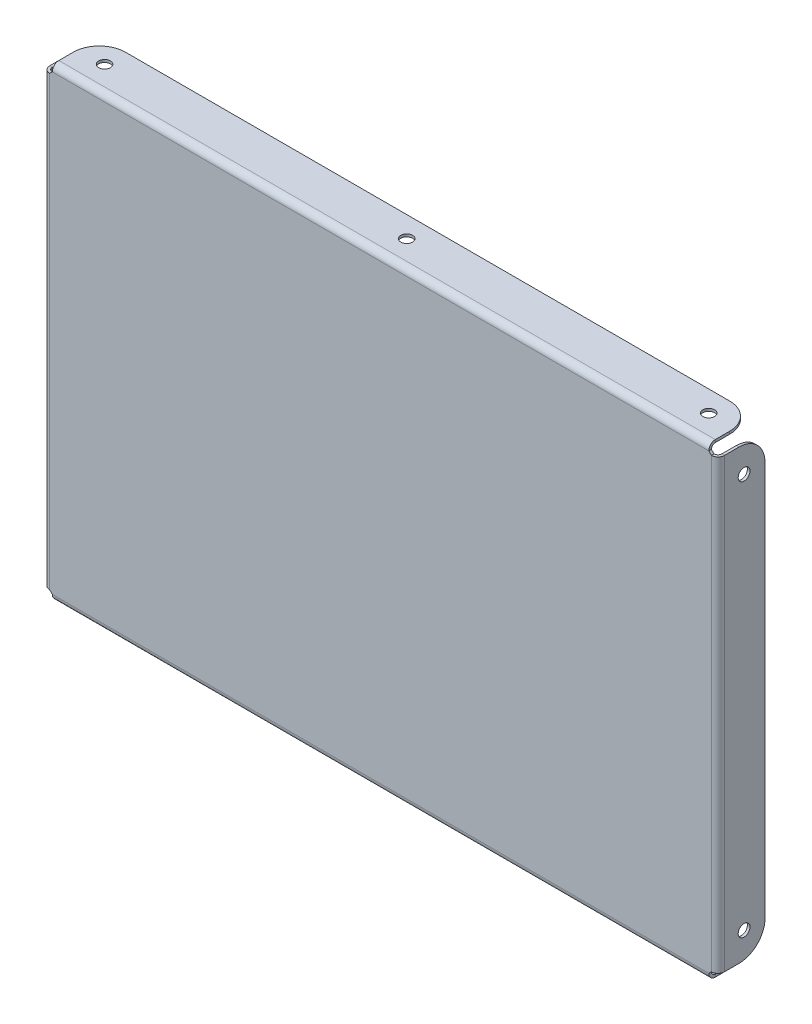
SolidWorks part; units mm, degrees
note: The reader was unsure of these and kept them because the rebuilt part matched: flange length of "Long Edge", "Short Edge".
material "1060-O (SS)"
ref_plane "Front Plane" through (0, 0, 0) normal (0, 0, 1) x (1, 0, 0)
ref_plane "Top Plane" through (0, 0, 0) normal (0, 1, 0) x (1, 0, 0)
ref_plane "Right Plane" through (0, 0, 0) normal (1, 0, 0) x (0, 0, -1)
sketch "Sketch1" plane through (0, 0, 0) normal (0, 0, 1) x (1, 0, 0)
  line L0 (-126.5, -85.5) -> (-125.5, -86.5)
  line L1 (-125.5, -86.5) -> (125.5, -86.5)
  line L2 (-126.5, -85.5) -> (-126.5, 85.5)
  line L3 (-125.5, 86.5) -> (125.5, 86.5)
  line L4 (126.5, -85.5) -> (126.5, 85.5)
  line L5 (-126.5, -86.5) -> (126.5, 86.5) construction
  line L6 (-126.5, 86.5) -> (126.5, -86.5) construction
  line L7 (125.5, -86.5) -> (126.5, -85.5)
  line L8 (125.5, 86.5) -> (126.5, 85.5)
  line L9 (-126.5, 85.5) -> (-125.5, 86.5)
  point P0 (0, 0)
  dimension "D1" = 253
  dimension "D2" = 173
base flange "Main Plate" sketch "Sketch1" thickness 1 reverse thickness direction no parameters "D1"=1.5
edge flange "Long Edge" sketch "Sketch9" flange angle 90 flange length 18 flange position bend outside bend radius 1.5 thickness 1 relief obround parameters "D6"=10
sketch "Sketch9" plane through (0, 86.5, -1) normal (0, 1, 0) x (1, 0, 0)
  line L2 (-125.5, 0) -> (-125.5, 17)
  line L3 (-125.5, 17) -> (125.5, 17)
  line L4 (125.5, 17) -> (125.5, 0)
  line L5 (125.5, 0) -> (-125.5, 0) construction
  line L6 (125.5, 0) -> (-125.5, 0)
bend "EdgeBend1" bend radius 1.5 bend angle 90 parameters "D5"=1
fillet "Long Edge Fillets" radius 10 2 edges at (-125.5, 88.5, -18) (125.5, 88.5, -18)
hole_wizard "M4 Clearance Hole1" positions "Sketch14" profile "Sketch15" hole size "M4" standard "ISO" end condition up to next
sketch "Sketch14" plane through (0, 89, 0) normal (0, 1, 0) x (1, 0, 0)
  line L0 (125.5, 0) -> (-125.5, 0) construction
  point P0 (-115.5, 10)
  point P2 (115.5, 10)
  point P4 (0, 10)
  dimension "D1" = 10
sketch "Sketch15" plane through (-115.5, 89, -10) normal (1, 0, 0) x (0, 0, 1)
  line L0 (0, 0) -> (0, 178)
  line L1 (0, 178) -> (2.25, 178)
  line L2 (2.25, 178) -> (2.25, 0)
  line L5 (2.25, 0) -> (0, 0)
  line L11 (0, -6.35) -> (0, 107.95) construction
  dimension "Thru Hole Dia." = 4.5
  dimension "Thru Hole Depth" = 178
edge flange "Short Edge" sketch "Sketch12" flange angle 90 flange length 18 flange position bend outside bend radius 1.5 thickness 1 relief obround parameters "D6"=10
sketch "Sketch12" plane through (126.5, 0, -1) normal (1, 0, 0) x (0, -1, 0)
  line L2 (-85.5, 0) -> (-85.5, 17)
  line L3 (-85.5, 17) -> (85.5, 17)
  line L4 (85.5, 17) -> (85.5, 0)
  line L5 (85.5, 0) -> (-85.5, 0) construction
  line L6 (85.5, 0) -> (-85.5, 0)
bend "EdgeBend2" bend radius 1.5 bend angle 90 parameters "D5"=3
fillet "Short Edge Fillets" radius 10 2 edges at (128.5, -85.5, -18) (128.5, 85.5, -18)
hole_wizard "M4 Clearance Hole2" positions "Sketch16" profile "Sketch17" hole size "M4" standard "ISO" end condition up to next
sketch "Sketch16" plane through (129, 0, 0) normal (1, 0, 0) x (0, 0, -1)
  line L0 (0, -85.5) -> (0, 85.5) construction
  point P0 (10, -75.5)
  point P2 (10, 75.5)
  dimension "D1" = 10
sketch "Sketch17" plane through (129, -75.5, -10) normal (0, 1, 0) x (0, 0, -1)
  line L0 (0, 0) -> (0, 258)
  line L1 (0, 258) -> (2.25, 258)
  line L2 (2.25, 258) -> (2.25, 0)
  line L5 (2.25, 0) -> (0, 0)
  line L11 (0, -6.35) -> (0, 107.95) construction
  dimension "Thru Hole Dia." = 4.5
  dimension "Thru Hole Depth" = 258
mirror "Other Long Edge" about plane through (0, 0, 0) normal (0, 1, 0) of "M4 Clearance Hole1", "Long Edge", "Long Edge Fillets"
bend "MirrorBend1" bend radius 1.5 bend angle 90 parameters "D5"=2
mirror "Other Short Edge" about plane through (0, 0, 0) normal (1, 0, 0) of "M4 Clearance Hole2", "Short Edge", "Short Edge Fillets"
bend "MirrorBend2" bend radius 1.5 bend angle 90 parameters "D5"=4
sketch "Bend-Lines1" [suppressed] plane through (0, 0, 0) normal (0, 1, 0) x (1, 0, 0)
sketch "Bounding-Box1" [suppressed] plane through (0, 0, 0) normal (0, 1, 0) x (1, 0, 0)
sheet metal parameters "Sheet-Metal1" thickness 1 parameters "D1"=1.5
flat pattern "Flat-Pattern1" [suppressed]
sketch "Bend-Lines2" plane through (0, 0, 0) normal (0, 1, 0) x (1, 0, 0)
sketch3d "Bounding-Box2" [suppressed]
  line L0 (-126.5, -86.5, 0) -> (126.5, -86.5, 0) construction
  line L1 (-126.5, 86.5, 0) -> (126.5, 86.5, 0) construction
  line L2 (-126.5, -86.5, 0) -> (-126.5, 86.5, 0) construction
  line L3 (126.5, -86.5, 0) -> (126.5, 86.5, 0) construction
sheet metal parameters "Sheet-Metal2" thickness 1 parameters "D1"=1.5
flat pattern "Flat-Pattern1"
sketch "Bend-Lines2" plane through (0, 0, 0) normal (0, 0, 1) x (1, 0, 0)
  line L0 (98.5, 88.0708) -> (-98.5, 88.0708) construction
  line L1 (98.5, 88.0708) -> (-98.5, 88.0708) construction
sketch3d "Bounding-Box2" [suppressed]
  line L0 (-126.5, -86.5, 0) -> (126.5, -86.5, 0) construction
  line L1 (-126.5, 105.1416, 0) -> (126.5, 105.1416, 0) construction
  line L2 (-126.5, -86.5, 0) -> (-126.5, 105.1416, 0) construction
  line L3 (126.5, -86.5, 0) -> (126.5, 105.1416, 0) construction
bend of the flat pattern "Flatten-<EdgeBend1>1"
sheet metal parameters "Sheet-Metal3" thickness 1 parameters "D1"=1.5
flat pattern "Flat-Pattern1" [suppressed]
sketch "Bend-Lines2" plane through (0, 0, 0) normal (0, 0, 1) x (1, 0, 0)
  line L0 (98.5, 88.0708) -> (-98.5, 88.0708) construction
  line L1 (98.5, 88.0708) -> (-98.5, 88.0708) construction
  line L2 (-98.5, -88.0708) -> (98.5, -88.0708) construction
  line L3 (-98.5, -88.0708) -> (98.5, -88.0708) construction
sketch3d "Bounding-Box2" [suppressed]
  line L0 (-126.5, -104.1416, 0) -> (126.5, -104.1416, 0) construction
  line L1 (-126.5, 104.1416, 0) -> (126.5, 104.1416, 0) construction
  line L2 (-126.5, -104.1416, 0) -> (-126.5, 104.1416, 0) construction
  line L3 (126.5, -104.1416, 0) -> (126.5, 104.1416, 0) construction
bend of the flat pattern "Flatten-<EdgeBend1>1"
bend of the flat pattern "Flatten-<MirrorBend1>1"
bend of the flat pattern "Flatten-<EdgeBend2>2"
sheet metal parameters "Sheet-Metal4" thickness 1 parameters "D1"=1.5
flat pattern "Flat-Pattern1"
sketch "Bend-Lines2" plane through (0, 0, 0) normal (0, 0, 1) x (1, 0, 0)
  line L0 (98.5, 88.0708) -> (-98.5, 88.0708) construction
  line L1 (98.5, 88.0708) -> (-98.5, 88.0708) construction
  line L4 (128.0708, -58.5) -> (128.0708, 58.5) construction
  line L5 (128.0708, -58.5) -> (128.0708, 58.5) construction
sketch3d "Bounding-Box2" [suppressed]
  line L0 (-126.5, -86.5, 0) -> (145.1416, -86.5, 0) construction
  line L1 (-126.5, 105.1416, 0) -> (145.1416, 105.1416, 0) construction
  line L2 (-126.5, -86.5, 0) -> (-126.5, 105.1416, 0) construction
  line L3 (145.1416, -86.5, 0) -> (145.1416, 105.1416, 0) construction
bend of the flat pattern "Flatten-<EdgeBend1>1"
bend of the flat pattern "Flatten-<EdgeBend2>1"
sheet metal parameters "Sheet-Metal5" thickness 1 parameters "D1"=1.5
flat pattern "Flat-Pattern1"
sketch "Bend-Lines2" plane through (0, 0, 0) normal (0, 0, 1) x (1, 0, 0)
  line L0 (125.5, 88.0708) -> (-125.5, 88.0708) construction
  line L1 (125.5, 88.0708) -> (-125.5, 88.0708) construction
  line L2 (-125.5, -88.0708) -> (125.5, -88.0708) construction
  line L3 (-125.5, -88.0708) -> (125.5, -88.0708) construction
  line L4 (128.0708, -85.5) -> (128.0708, 85.5) construction
  line L5 (128.0708, -85.5) -> (128.0708, 85.5) construction
  line L6 (-128.0708, 85.5) -> (-128.0708, -85.5) construction
  line L7 (-128.0708, 85.5) -> (-128.0708, -85.5) construction
sketch3d "Bounding-Box2" [suppressed]
  line L0 (-145.1416, -105.1416, 0) -> (145.1416, -105.1416, 0) construction
  line L1 (-145.1416, 105.1416, 0) -> (145.1416, 105.1416, 0) construction
  line L2 (-145.1416, -105.1416, 0) -> (-145.1416, 105.1416, 0) construction
  line L3 (145.1416, -105.1416, 0) -> (145.1416, 105.1416, 0) construction
bend of the flat pattern "Flatten-<EdgeBend1>1"
bend of the flat pattern "Flatten-<MirrorBend1>1"
bend of the flat pattern "Flatten-<EdgeBend2>1"
bend of the flat pattern "Flatten-<MirrorBend2>1"
sheet metal parameters "Sheet-Metal6" [suppressed] thickness 1 parameters "D1"=1.5
flat pattern "Flat-Pattern1"
sketch "Bend-Lines2" plane through (0, 0, 0) normal (0, 0, 1) x (1, 0, 0)
  line L0 (98.5, 88.0708) -> (-98.5, 88.0708) construction
  line L1 (98.5, 88.0708) -> (-98.5, 88.0708) construction
sketch3d "Bounding-Box2" [suppressed]
  line L0 (-126.5, -86.5, 0) -> (126.5, -86.5, 0) construction
  line L1 (-126.5, 105.1416, 0) -> (126.5, 105.1416, 0) construction
  line L2 (-126.5, -86.5, 0) -> (-126.5, 105.1416, 0) construction
  line L3 (126.5, -86.5, 0) -> (126.5, 105.1416, 0) construction
bend of the flat pattern "Flatten-<EdgeBend1>1"
sheet metal parameters "Sheet-Metal7" [suppressed] thickness 1 parameters "D1"=1.5
flat pattern "Flat-Pattern1"
sketch "Bend-Lines2" plane through (0, 0, 0) normal (0, 0, 1) x (1, 0, 0)
  line L0 (98.5, 88.0708) -> (-98.5, 88.0708) construction
  line L1 (98.5, 88.0708) -> (-98.5, 88.0708) construction
  line L4 (128.0708, -58.5) -> (128.0708, 58.5) construction
  line L5 (128.0708, -58.5) -> (128.0708, 58.5) construction
sketch3d "Bounding-Box2" [suppressed]
  line L0 (-126.5, -86.5, 0) -> (145.1416, -86.5, 0) construction
  line L1 (-126.5, 105.1416, 0) -> (145.1416, 105.1416, 0) construction
  line L2 (-126.5, -86.5, 0) -> (-126.5, 105.1416, 0) construction
  line L3 (145.1416, -86.5, 0) -> (145.1416, 105.1416, 0) construction
bend of the flat pattern "Flatten-<EdgeBend1>1"
bend of the flat pattern "Flatten-<EdgeBend2>1"
